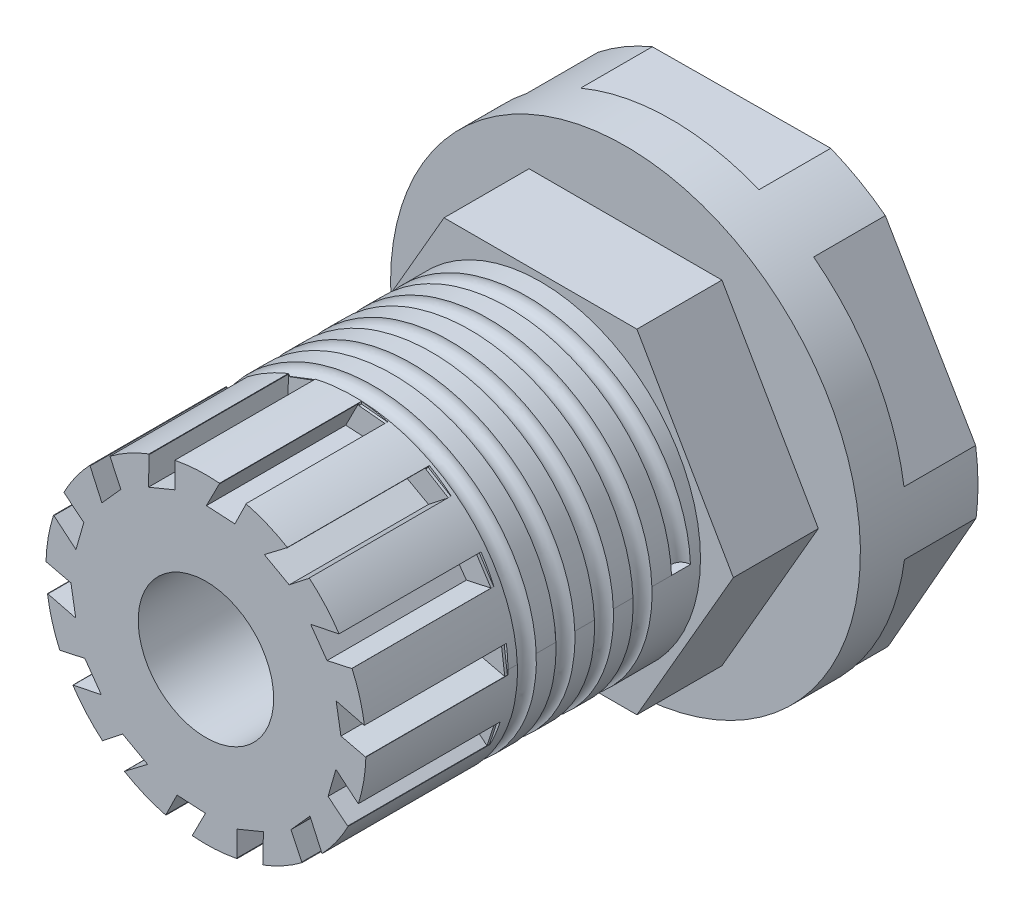
SolidWorks part; units mm, degrees
ref_plane "Front Plane" through (0, 0, 0) normal (0, 0, 1) x (1, 0, 0)
ref_plane "Top Plane" through (0, 0, 0) normal (0, 1, 0) x (1, 0, 0)
ref_plane "Right Plane" through (0, 0, 0) normal (1, 0, 0) x (0, 0, -1)
sketch "Sketch1" plane through (0, 0, 0) normal (0, 0, 1) x (1, 0, 0)
  circle A0 centre (0, 0) radius 9.13
  dimension "D1" = 18.26
extrude "Boss-Extrude1" add sketch "Sketch1" against normal blind 19.09
sketch "Sketch2" plane through (0, 0, -19.09) normal (0, 0, -1) x (-1, 0, 0)
  circle A0 centre (0, 0) radius 11.93
  dimension "D1" = 23.86
extrude "Boss-Extrude2" add sketch "Sketch2" along normal blind 4.85
sketch "Sketch3" plane through (0, 0, -23.94) normal (0, 0, -1) x (-1, 0, 0)
  circle A0 centre (0, 0) radius 13.405
  dimension "D1" = 26.81
extrude "Boss-Extrude3" add sketch "Sketch3" along normal blind 6.71
sketch "Sketch4" plane through (0, 0, -30.65) normal (0, 0, -1) x (-1, 0, 0)
  circle A0 centre (0, 0) radius 9.155
  dimension "D1" = 18.31
extrude "Boss-Extrude4" add sketch "Sketch4" along normal blind 1.85
sketch "Sketch5" plane through (0, 0, 0) normal (0, 0, 1) x (1, 0, 0)
  circle A0 centre (0, 0) radius 3.865
  dimension "D1" = 7.73
extrude "Cut-Extrude1" cut sketch "Sketch5" against normal blind 35
sketch "Sketch6" plane through (0, 0, -19.09) normal (0, 0, 1) x (1, 0, 0)
  line L0 (-7.177, 9.5298) -> (7.177, 9.5298)
  line L1 (7.177, 9.5298) -> (7.177, 11.93)
  line L2 (7.177, 11.93) -> (-7.177, 11.93)
  line L3 (-7.177, 11.93) -> (-7.177, 9.5298)
  circle A0 centre (0, 0) radius 11.93 construction
extrude "Cut-Extrude3" cut sketch "Sketch6" against normal blind 4.85
sketch "Sketch7" plane through (0, 0, 0) normal (0, 0, 1) x (1, 0, 0)
  point P0 (0, 0)
pattern_circular "CirPattern1" count 6 over 360 about axis through (0, 0, 0) along (0, 0, 1) of "Cut-Extrude3"
sketch "Sketch8" plane through (0, 0, -30.65) normal (0, 0, -1) x (-1, 0, 0)
  line L4 (-5.0016, 12.437) -> (5.1798, 12.3638)
  line L5 (5.1798, 12.3638) -> (5.1798, 14.6611)
  line L6 (5.1798, 14.6611) -> (-5.2195, 14.7359)
  line L7 (-5.2195, 14.7359) -> (-5.0016, 12.437)
  circle A2 centre (0, 0) radius 13.405 construction
extrude "Cut-Extrude4" cut sketch "Sketch8" against normal blind 4.09
pattern_circular "CirPattern2" count 6 over 360 about axis through (0, 0, 0) along (0, 0, 1) of "Cut-Extrude4"
sketch "Sketch11" plane through (0, 0, -19.09) normal (0, 0, 1) x (1, 0, 0)
  circle A0 centre (0, 0) radius 9.13 construction
  circle A1 centre (0, 0) radius 9.13
curve "Helix/Spiral1" pitch 2.2 height 11 turns 5
sketch "Sketch12" plane through (0, 0, 0) normal (0, 1, 0) x (1, 0, 0)
  circle A1 centre (9.1232, 17.9765) radius 0.5399
  spline S1 degree 3 poles (-9.13, 19.09) (-9.13, 19.0445) (-8.6546, 18.9524) (-6.624, 18.815) (-3.5849, 18.6775) (0, 18.54) (3.5849, 18.4025) (6.624, 18.265) (8.6546, 18.1275) (9.3677, 17.99) (8.6546, 17.8525) (6.624, 17.715) (2.5718, 17.5317) (-2.5718, 17.3483) (-6.624, 17.165) (-8.6546, 17.0275) (-9.3677, 16.89) (-8.6546, 16.7525) (-6.624, 16.615) (-2.5718, 16.4317) (2.5718, 16.2483) (6.624, 16.065) (8.6546, 15.9275) (9.3677, 15.79) (8.6546, 15.6525) (6.624, 15.515) (2.5718, 15.3317) (-2.5718, 15.1483) (-6.624, 14.965) (-8.6546, 14.8275) (-9.3677, 14.69) (-8.6546, 14.5525) (-6.624, 14.415) (-2.5718, 14.2317) (2.5718, 14.0483) (6.624, 13.865) (8.6546, 13.7275) (9.3677, 13.59) (8.6546, 13.4525) (6.624, 13.315) (2.5718, 13.1317) (-2.5718, 12.9483) (-6.624, 12.765) (-8.6546, 12.6275) (-9.3677, 12.49) (-8.6546, 12.3525) (-6.624, 12.215) (-2.5718, 12.0317) (2.5718, 11.8483) (6.624, 11.665) (8.6546, 11.5275) (9.3677, 11.39) (8.6546, 11.2525) (6.624, 11.115) (2.5718, 10.9317) (-2.5718, 10.7483) (-6.624, 10.565) (-8.6546, 10.4275) (-9.3677, 10.29) (-8.6546, 10.1525) (-6.624, 10.015) (-2.5718, 9.8317) (2.5718, 9.6483) (6.624, 9.465) (8.6546, 9.3275) (9.3677, 9.19) (8.6546, 9.0525) (6.624, 8.915) (3.5849, 8.7775) (0, 8.64) (-3.5849, 8.5025) (-6.624, 8.365) (-8.6546, 8.2276) (-9.13, 8.1355) (-9.13, 8.09) knots 0 0 0 0 0.0125 0.025 0.0375 0.05 0.0625 0.075 0.0875 0.1 0.1125 0.125 0.1375 0.1625 0.175 0.1875 0.2 0.2125 0.225 0.2375 0.2625 0.275 0.2875 0.3 0.3125 0.325 0.3375 0.3625 0.375 0.3875 0.4 0.4125 0.425 0.4375 0.4625 0.475 0.4875 0.5 0.5125 0.525 0.5375 0.5625 0.575 0.5875 0.6 0.6125 0.625 0.6375 0.6625 0.675 0.6875 0.7 0.7125 0.725 0.7375 0.7625 0.775 0.7875 0.8 0.8125 0.825 0.8375 0.8625 0.875 0.8875 0.9 0.9125 0.925 0.9375 0.95 0.9625 0.975 0.9875 1 1 1 1 construction
sweep "Cut-Sweep1" cut profiles "Sketch12" path "Helix/Spiral1"
fillet "Fillet1" radius 1 1 edges at (-9.155, 0, -32.5)
sketch "Sketch15" plane through (0, 0, 0) normal (0, 0, 1) x (1, 0, 0)
  line L0 (0.7713, 9.0719) -> (0.0274, 7.6152)
  line L1 (1.6494, 7.5241) -> (2.2842, 8.8143)
  line L2 (0.0274, 7.6152) -> (1.6494, 7.5241)
  circle A0 centre (0, 0) radius 6.2
  arc A2 (-0.7164, 6.1585) -> (0.961, 6.1251) centre (0, 0) cw
  arc A4 (0.7713, 9.0719) -> (2.2842, 8.8143) centre (-0.4428, -2.6306) cw
  dimension "D1" = 12.4
extrude "Cut-Extrude6" cut sketch "Sketch15" against normal blind 7.95 contours A4 L0 A0 L1
sketch "Sketch16" plane through (0, 0, 0) normal (0, 0, 1) x (1, 0, 0)
  line L0 (0.777, 9.1688) -> (0.777, 8.9583)
  line L1 (0.777, 8.9583) -> (2.2842, 8.8143)
  line L2 (2.2842, 8.8143) -> (2.2842, 9.1688)
  line L3 (2.2842, 9.1688) -> (0.777, 9.1688)
extrude "Cut-Extrude7" cut sketch "Sketch16" against normal blind 8.1
pattern_circular "CirPattern3" count 14 over 360 about axis through (0, 0, 0) along (0, 0, 1) of "Cut-Extrude6"
pattern_circular "CirPattern4" count 14 over 360 about axis through (0, 0, 0) along (0, 0, 1) of "Cut-Extrude7"
